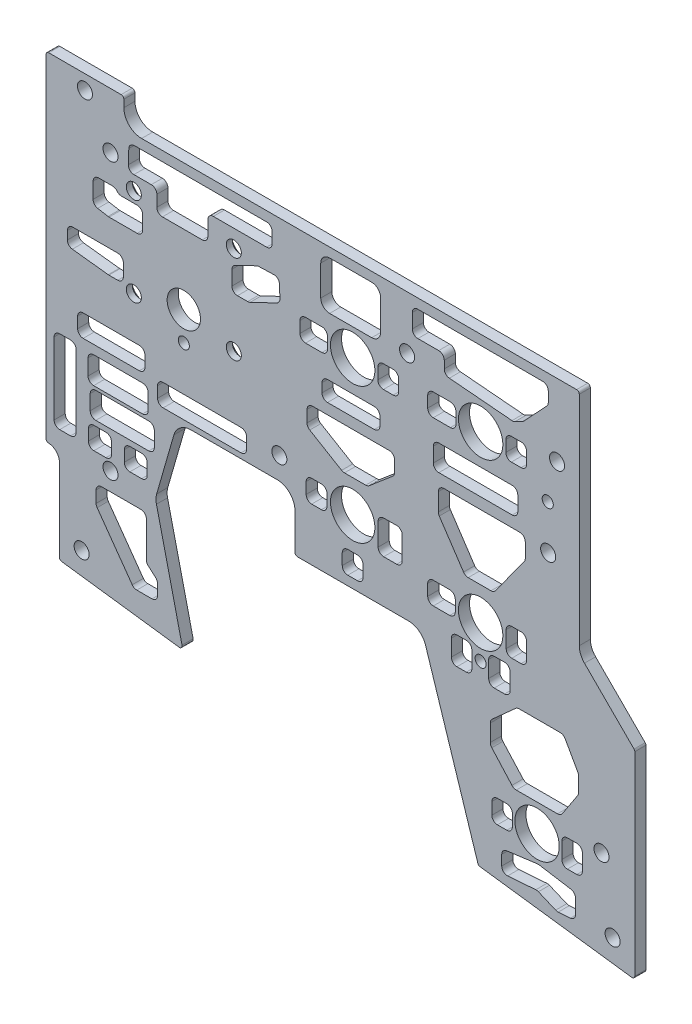
SolidWorks part; units mm, degrees
ref_plane "Front Plane" through (0, 0, 0) normal (0, 0, 1) x (1, 0, 0)
ref_plane "Top Plane" through (0, 0, 0) normal (0, 1, 0) x (1, 0, 0)
ref_plane "Right Plane" through (0, 0, 0) normal (1, 0, 0) x (0, 0, -1)
sketch "Sketch1" plane through (0, 0, 0) normal (0, 0, 1) x (1, 0, 0)
  line L16 (3.81, -91.8845) -> (3.81, -115.4033)
  line L17 (4.4725, -116.1588) -> (38.0231, -120.5758)
  line L18 (38.8645, -119.6465) -> (31.5446, -88.4134)
  line L19 (31.6093, -85.8475) -> (36.5334, -68.7608)
  line L20 (41.4148, -65.0875) -> (66.04, -65.0875)
  line L21 (71.12, -70.1675) -> (71.12, -80.518)
  line L22 (71.882, -81.28) -> (103.6122, -81.28)
  line L23 (108.4484, -84.805) -> (123.4233, -131.3792)
  line L24 (124.0493, -131.9014) -> (167.4135, -137.6104)
  line L25 (168.275, -136.8549) -> (168.275, -81.3036)
  line L26 (168.0518, -80.7647) -> (153.8879, -66.6008)
  line L27 (152.4, -63.0087) -> (152.4, -0.762)
  line L28 (151.638, 0) -> (27.305, 0)
  line L29 (22.225, 5.08) -> (22.225, 7.1755)
  line L30 (21.463, 7.9375) -> (0.762, 7.9375)
  line L31 (0, 7.1755) -> (0, -87.9495)
  line L32 (3.81, -91.8845) -> (3.81, -115.4033)
  line L33 (4.4725, -116.1588) -> (38.0231, -120.5758)
  line L34 (38.8645, -119.6465) -> (31.5446, -88.4134)
  line L35 (31.6093, -85.8475) -> (36.5334, -68.7608)
  line L36 (41.4148, -65.0875) -> (66.04, -65.0875)
  line L37 (71.12, -70.1675) -> (71.12, -80.518)
  line L38 (71.882, -81.28) -> (103.6122, -81.28)
  line L39 (108.4484, -84.805) -> (123.4233, -131.3792)
  line L40 (124.0493, -131.9014) -> (167.4135, -137.6104)
  line L41 (168.275, -136.8549) -> (168.275, -81.3036)
  line L42 (168.0518, -80.7647) -> (153.8879, -66.6008)
  line L43 (152.4, -63.0087) -> (152.4, -0.762)
  line L44 (151.638, 0) -> (27.305, 0)
  line L45 (22.225, 5.08) -> (22.225, 7.1755)
  line L46 (21.463, 7.9375) -> (0.762, 7.9375)
  line L47 (0, 7.1755) -> (0, -87.9495)
  arc A17 (3.81, -91.8845) -> (0.7374, -88.7112) centre (0.635, -91.8845) ccw
  arc A18 (3.81, -115.4033) -> (4.4725, -116.1588) centre (4.572, -115.4033) ccw
  arc A19 (38.0231, -120.5758) -> (38.8645, -119.6465) centre (38.1226, -119.8204) ccw
  arc A20 (31.6093, -85.8475) -> (31.5446, -88.4134) centre (36.4906, -87.2542) ccw
  arc A21 (41.4148, -65.0875) -> (36.5334, -68.7608) centre (41.4148, -70.1675) ccw
  arc A22 (71.12, -70.1675) -> (66.04, -65.0875) centre (66.04, -70.1675) ccw
  arc A23 (71.12, -80.518) -> (71.882, -81.28) centre (71.882, -80.518) ccw
  arc A24 (108.4484, -84.805) -> (103.6122, -81.28) centre (103.6122, -86.36) ccw
  arc A25 (123.4233, -131.3792) -> (124.0493, -131.9014) centre (124.1487, -131.1459) ccw
  arc A26 (167.4135, -137.6104) -> (168.275, -136.8549) centre (167.513, -136.8549) ccw
  arc A27 (168.275, -81.3036) -> (168.0518, -80.7647) centre (167.513, -81.3036) ccw
  arc A28 (152.4, -63.0087) -> (153.8879, -66.6008) centre (157.48, -63.0087) ccw
  arc A29 (152.4, -0.762) -> (151.638, 0) centre (151.638, -0.762) ccw
  arc A30 (22.225, 5.08) -> (27.305, 0) centre (27.305, 5.08) ccw
  arc A31 (22.225, 7.1755) -> (21.463, 7.9375) centre (21.463, 7.1755) ccw
  arc A32 (0.762, 7.9375) -> (0, 7.1755) centre (0.762, 7.1755) ccw
  arc A33 (0, -87.9495) -> (0.7374, -88.7112) centre (0.762, -87.9495) ccw
  arc A34 (3.81, -91.8845) -> (0.7374, -88.7112) centre (0.635, -91.8845) ccw
  arc A35 (3.81, -115.4033) -> (4.4725, -116.1588) centre (4.572, -115.4033) ccw
  arc A36 (38.0231, -120.5758) -> (38.8645, -119.6465) centre (38.1226, -119.8204) ccw
  arc A37 (31.6093, -85.8475) -> (31.5446, -88.4134) centre (36.4906, -87.2542) ccw
  arc A38 (41.4148, -65.0875) -> (36.5334, -68.7608) centre (41.4148, -70.1675) ccw
  arc A39 (71.12, -70.1675) -> (66.04, -65.0875) centre (66.04, -70.1675) ccw
  arc A40 (71.12, -80.518) -> (71.882, -81.28) centre (71.882, -80.518) ccw
  arc A41 (108.4484, -84.805) -> (103.6122, -81.28) centre (103.6122, -86.36) ccw
  arc A42 (123.4233, -131.3792) -> (124.0493, -131.9014) centre (124.1487, -131.1459) ccw
  arc A43 (167.4135, -137.6104) -> (168.275, -136.8549) centre (167.513, -136.8549) ccw
  arc A44 (168.275, -81.3036) -> (168.0518, -80.7647) centre (167.513, -81.3036) ccw
  arc A45 (152.4, -63.0087) -> (153.8879, -66.6008) centre (157.48, -63.0087) ccw
  arc A46 (152.4, -0.762) -> (151.638, 0) centre (151.638, -0.762) ccw
  arc A47 (22.225, 5.08) -> (27.305, 0) centre (27.305, 5.08) ccw
  arc A48 (22.225, 7.1755) -> (21.463, 7.9375) centre (21.463, 7.1755) ccw
  arc A49 (0.762, 7.9375) -> (0, 7.1755) centre (0.762, 7.1755) ccw
  arc A50 (0, -87.9495) -> (0.7374, -88.7112) centre (0.762, -87.9495) ccw
  dimension "D1" = 0
extrude "Boss-Extrude1" add sketch "Sketch1" against normal blind 3.175
hole_wizard "#6 Clearance Hole1" positions "Sketch3" profile "Sketch2" hole size "#6" standard "ANSI Inch" end condition through all
sketch "Sketch3" plane through (0, 0, -3.175) normal (0, 0, -1) x (-1, 0, 0)
  point P0 (-11.1125, 3.81)
  point P3 (-18.415, -7.9375)
  point P6 (-103.1875, -15.24)
  point P9 (-143.51, -44.45)
  point P12 (-158.75, -111.125)
  point P15 (-18.415, -86.741)
  point P18 (-66.675, -58.7375)
  point P21 (-10.16, -110.5028)
  point P25 (-146.05, -20.6375)
  point P28 (-161.925, -130.483)
sketch "Sketch2" plane through (11.1125, 3.81, -3.175) normal (1, 0, 0) x (0, 1, 0)
  line L0 (0, 0) -> (0, 3.175)
  line L1 (0, 3.175) -> (2.1526, 3.175)
  line L2 (2.1526, 3.175) -> (2.1526, 0)
  line L5 (2.1526, 0) -> (0, 0)
  line L11 (0, -6.35) -> (0, 107.95) construction
  dimension "Thru Hole Dia." = 4.3053
  dimension "Thru Hole Depth" = 3.175
sketch "Sketch4" plane through (0, 0, -3.175) normal (0, 0, -1) x (-1, 0, 0)
  circle A0 centre (-140.335, -115.57) radius 6.35
  circle A1 centre (-124.206, -71.4375) radius 6.35
  circle A2 centre (-87.63, -62.992) radius 6.35
  circle A3 centre (-87.63, -24.13) radius 6.35
  circle A4 centre (-124.206, -24.13) radius 6.35
  circle A5 centre (-124.206, -80.9625) radius 1.5875
  circle A6 centre (-39.37, -36.322) radius 4.7625
  dimension "D1" = 12.7
  dimension "D2" = 3.175
  dimension "D4" = 9.525
  dimension "D3" = 9.525
extrude "Cut-Extrude1" cut sketch "Sketch4" against normal through all
hole_wizard "CSK for #6 Flat Head Machine Screw (100)1" positions "Sketch6" profile "Sketch5" countersink size "#6" standard "ANSI Inch" end condition through all
sketch "Sketch6" plane through (0, 0, -3.175) normal (0, 0, -1) x (-1, 0, 0)
  point P0 (-53.6575, -14.097)
  point P2 (-25.0825, -14.097)
  point P4 (-25.0825, -39.497)
  point P6 (-53.6575, -39.497)
sketch "Sketch5" plane through (53.6575, -14.097, -3.175) normal (1, 0, 0) x (0, 1, 0)
  line L0 (0, 0) -> (0, 3.175)
  line L1 (0, 3.175) -> (2.1526, 3.175)
  line L2 (2.1526, 3.175) -> (2.1526, 1.4209)
  line L3 (2.1526, 1.4209) -> (3.846, 0)
  line L5 (3.846, 0) -> (0, 0)
  line L6 (-2.1526, 1.4209) -> (-3.846, 0) construction
  line L11 (0, -6.35) -> (0, 107.95) construction
  dimension "Thru Hole Dia." = 4.3053
  dimension "Thru Hole Depth" = 3.175
  dimension "Near C'Sink Dia." = 7.692
  dimension "Near C'Sink Angle" = 100
hole_wizard "#0 Clearance Hole1" positions "Sketch7" profile "Sketch8" hole size "#0" standard "ANSI Inch" end condition through all
sketch "Sketch7" plane through (0, 0, -9.525) normal (0, 0, -1) x (-1, 0, 0)
  point P0 (-39.37, -44.577)
sketch "Sketch8" plane through (39.37, -44.577, -9.525) normal (1, 0, 0) x (0, 1, 0)
  line L0 (0, 0) -> (0, 9.525)
  line L1 (0, 9.525) -> (0.9271, 9.525)
  line L2 (0.9271, 9.525) -> (0.9271, 0)
  line L3 (0.9271, 0) -> (0, 0)
  line L4 (0, -6.35) -> (0, 107.95) construction
  dimension "Thru Hole Dia." = 1.8542
  dimension "Thru Hole Depth" = 9.525
hole_wizard "1/8 (0.125) Diameter Hole1" positions "Sketch9" profile "Sketch10" hole size "1/8" standard "ANSI Inch" end condition through all
sketch "Sketch9" plane through (0, 0, 0) normal (0, 0, 1) x (1, 0, 0)
  point P0 (39.37, -44.577)
sketch "Sketch10" plane through (39.37, -44.577, 0) normal (1, 0, 0) x (0, -1, 0)
  line L0 (0, 0) -> (0, 3.175)
  line L1 (0, 3.175) -> (1.5875, 3.175)
  line L2 (1.5875, 3.175) -> (1.5875, 0)
  line L5 (1.5875, 0) -> (0, 0)
  line L11 (0, -6.35) -> (0, 107.95) construction
  dimension "Thru Hole Dia." = 3.175
  dimension "Thru Hole Depth" = 3.175
sketch "Sketch17" plane through (0, 0, 0) normal (0, 0, -1) x (-1, 0, 0)
  line L0 (-141.9544, -2.7948) -> (-106.2662, -2.7948)
  line L1 (-104.6787, -4.3823) -> (-104.6787, -8.4606)
  line L2 (-106.2662, -10.0481) -> (-112.2209, -10.0481)
  line L3 (-113.8084, -11.6356) -> (-113.8084, -13.7762)
  line L4 (-115.259, -15.3578) -> (-133.159, -16.9076)
  line L5 (-134.0131, -16.7423) -> (-136.0874, -15.6921)
  line L6 (-136.5298, -15.36) -> (-143.114, -8.3185)
  line L7 (-143.5419, -7.2342) -> (-143.5419, -4.3823)
  line L8 (-93.0669, -2.7076) -> (-81.0441, -2.7076)
  line L9 (-78.5041, -5.2476) -> (-78.5041, -13.8956)
  line L10 (-81.0441, -16.4356) -> (-93.0669, -16.4356)
  line L11 (-95.6069, -13.8956) -> (-95.6069, -5.2476)
  line L12 (-72.5612, -22.437) -> (-72.5612, -25.637)
  line L13 (-74.1487, -27.2245) -> (-78.851, -27.2245)
  line L14 (-80.4385, -25.637) -> (-80.4385, -22.437)
  line L15 (-74.1487, -20.8495) -> (-78.851, -20.8495)
  line L16 (-99.2018, -21.1963) -> (-96.4213, -21.1963)
  line L17 (-94.8338, -22.7838) -> (-94.8338, -25.9818)
  line L18 (-96.4213, -27.5693) -> (-99.2018, -27.5693)
  line L19 (-100.7893, -25.9818) -> (-100.7893, -22.7838)
  line L20 (-109.0792, -22.6549) -> (-109.0792, -25.8549)
  line L21 (-110.6667, -27.4424) -> (-115.5536, -27.4424)
  line L22 (-117.1411, -25.8549) -> (-117.1411, -22.6549)
  line L23 (-110.6667, -21.0674) -> (-115.5536, -21.0674)
  line L24 (-135.7738, -20.8814) -> (-132.9933, -20.8814)
  line L25 (-131.4058, -22.4689) -> (-131.4058, -25.667)
  line L26 (-132.9933, -27.2545) -> (-135.7738, -27.2545)
  line L27 (-137.3613, -25.667) -> (-137.3613, -22.4689)
  line L28 (-93.8189, -33.0853) -> (-80.4385, -33.0853)
  line L29 (-78.851, -34.6728) -> (-78.851, -37.1954)
  line L30 (-80.4385, -38.7829) -> (-93.8189, -38.7829)
  line L31 (-95.4064, -34.6728) -> (-95.4064, -37.1954)
  line L32 (-133.2346, -32.9063) -> (-112.2542, -32.9063)
  line L33 (-110.6667, -34.4938) -> (-110.6667, -38.6545)
  line L34 (-112.2542, -40.242) -> (-133.2346, -40.242)
  line L35 (-134.8221, -38.6545) -> (-134.8221, -34.4938)
  line L36 (-98.0498, -41.8469) -> (-76.1717, -41.8469)
  line L37 (-74.5842, -43.4344) -> (-74.5842, -46.7771)
  line L38 (-75.3596, -48.1412) -> (-84.4657, -53.5626)
  line L39 (-85.2778, -53.7861) -> (-91.3474, -53.7861)
  line L40 (-92.3756, -53.4081) -> (-99.0779, -47.711)
  line L41 (-99.6373, -46.5014) -> (-99.6373, -43.4344)
  line L42 (-135.3789, -43.4344) -> (-113.699, -43.4344)
  line L43 (-112.1115, -45.0219) -> (-112.1115, -50.0429)
  line L44 (-112.3789, -50.9245) -> (-119.3229, -61.3222)
  line L45 (-120.6431, -62.0281) -> (-127.1632, -62.0281)
  line L46 (-128.4485, -61.3724) -> (-136.6641, -50.0405)
  line L47 (-136.9664, -49.1087) -> (-136.9664, -45.0219)
  line L48 (-55.7285, -57.3176) -> (-33.4587, -57.3176)
  line L49 (-31.8712, -58.9051) -> (-31.8712, -62.02)
  line L50 (-33.4587, -63.6075) -> (-55.7285, -63.6075)
  line L51 (-57.316, -62.02) -> (-57.316, -58.9051)
  line L52 (-78.7021, -59.8174) -> (-75.9216, -59.8174)
  line L53 (-74.3341, -61.4049) -> (-74.3341, -64.603)
  line L54 (-75.9216, -66.1905) -> (-78.7021, -66.1905)
  line L55 (-80.2896, -64.603) -> (-80.2896, -61.4049)
  line L56 (-89.0189, -72.2548) -> (-86.2384, -72.2548)
  line L57 (-84.6509, -73.8423) -> (-84.6509, -77.0403)
  line L58 (-86.2384, -78.6278) -> (-89.0189, -78.6278)
  line L59 (-90.6064, -77.0403) -> (-90.6064, -73.8423)
  line L60 (-109.0756, -69.248) -> (-109.0756, -72.448)
  line L61 (-110.6631, -74.0355) -> (-115.3654, -74.0355)
  line L62 (-116.9529, -72.448) -> (-116.9529, -69.248)
  line L63 (-110.6631, -67.6605) -> (-115.3654, -67.6605)
  line L64 (-148.3701, -88.0766) -> (-151.9572, -94.4661)
  line L65 (-152.1698, -95.2794) -> (-152.1698, -99.4916)
  line L66 (-151.8961, -100.4052) -> (-147.5598, -106.9917)
  line L68 (-146.1721, -107.7395) -> (-134.3926, -107.7395)
  line L70 (-133.1575, -107.1893) -> (-127.3956, -100.785)
  line L71 (-126.9693, -99.6738) -> (-126.9693, -94.8668)
  line L72 (-127.5195, -93.6317) -> (-134.1629, -87.6548)
  line L73 (-135.2742, -87.2285) -> (-146.9213, -87.2285)
  line L74 (-137.3613, -69.4742) -> (-137.3613, -74.1715)
  line L75 (-135.7738, -75.759) -> (-133.0932, -75.759)
  line L76 (-131.5057, -74.1715) -> (-131.5057, -69.4818)
  line L77 (-133.0887, -67.8943) -> (-135.7692, -67.8867)
  line L78 (-132.6264, -79.3569) -> (-132.6264, -84.055)
  line L79 (-131.0389, -85.6425) -> (-128.0874, -85.6425)
  line L80 (-126.4999, -84.055) -> (-126.4999, -79.3653)
  line L81 (-128.0829, -77.7778) -> (-131.0344, -77.7694)
  line L82 (-121.6938, -79.414) -> (-121.6938, -84.1113)
  line L83 (-120.1063, -85.6988) -> (-117.4258, -85.6988)
  line L84 (-115.8383, -84.1113) -> (-115.8383, -79.4216)
  line L85 (-117.4212, -77.8341) -> (-120.1018, -77.8265)
  line L86 (-101.7978, -60.9375) -> (-101.7978, -67.3473)
  line L87 (-100.2103, -68.9348) -> (-96.4976, -68.9348)
  line L88 (-94.9101, -67.3473) -> (-94.9101, -60.9481)
  line L89 (-96.4931, -59.3606) -> (-100.2058, -59.35)
  line L90 (-153.2801, -113.8454) -> (-153.2801, -118.4115)
  line L91 (-151.6926, -119.999) -> (-149.0121, -119.999)
  line L92 (-147.4246, -118.4115) -> (-147.4246, -113.853)
  line L93 (-149.0076, -112.2655) -> (-151.6881, -112.2579)
  line L94 (-133.2696, -114.0603) -> (-133.2696, -117.4522)
  line L95 (-131.6821, -119.0397) -> (-129.0016, -119.0397)
  line L96 (-127.4141, -117.4522) -> (-127.4141, -114.0679)
  line L97 (-128.997, -112.4804) -> (-131.6776, -112.4728)
  line L98 (-150.0084, -124.4751) -> (-140.8902, -122.9925)
  line L99 (-140.4256, -122.9858) -> (-131.6139, -124.1607)
  line L100 (-130.2362, -125.7343) -> (-130.2362, -128.6297)
  line L101 (-131.9392, -130.213) -> (-139.9781, -129.6268)
  line L102 (-140.7126, -129.7482) -> (-145.6471, -131.838)
  line L103 (-146.3817, -131.9595) -> (-149.8691, -131.7052)
  line L104 (-151.3411, -130.1219) -> (-151.3411, -126.042)
  line L105 (-63.0404, -2.7948) -> (-25.2277, -2.7948)
  line L106 (-23.641, -4.3315) -> (-23.5105, -8.4099)
  line L107 (-25.0972, -10.0481) -> (-30.0725, -10.0481)
  line L108 (-31.66, -11.6356) -> (-31.66, -14.8481)
  line L109 (-33.2475, -16.4356) -> (-44.6401, -16.4356)
  line L110 (-46.2276, -14.8481) -> (-46.2276, -10.6224)
  line L111 (-47.8151, -9.0349) -> (-63.0404, -9.0349)
  line L112 (-64.6279, -7.4474) -> (-64.6279, -4.3823)
  line L113 (-14.7591, -23.5708) -> (-17.7234, -24.0903)
  line L114 (-17.9974, -24.1142) -> (-26.0381, -24.1142)
  line L115 (-27.6256, -22.5267) -> (-27.6256, -18.7366)
  line L116 (-26.0381, -17.1491) -> (-21.5632, -17.1491)
  line L117 (-20.4504, -16.6939) -> (-20.1204, -16.3695)
  line L118 (-19.0076, -15.9142) -> (-15.0331, -15.9142)
  line L119 (-13.4456, -17.5017) -> (-13.4456, -22.0071)
  line L120 (-7.6875, -31.7843) -> (-20.4927, -31.7843)
  line L121 (-22.0802, -33.3718) -> (-22.0802, -36.9105)
  line L122 (-20.4927, -38.498) -> (-17.9504, -38.498)
  line L123 (-17.7686, -38.4875) -> (-7.5058, -37.3048)
  line L124 (-6.1, -35.7277) -> (-6.1, -33.3718)
  line L125 (-54.0177, -18.0353) -> (-60.157, -15.0963)
  line L126 (-60.7931, -14.9415) -> (-65.0805, -14.8081)
  line L127 (-66.7166, -16.3454) -> (-66.8282, -19.9294)
  line L128 (-65.9269, -21.4107) -> (-58.3022, -25.0607)
  line L129 (-57.6167, -25.2163) -> (-54.7032, -25.2163)
  line L130 (-53.1157, -23.6288) -> (-53.1157, -19.4672)
  line L131 (-24.6224, -111.8142) -> (-14.5986, -97.7476)
  line L132 (-14.304, -96.8263) -> (-14.304, -93.5113)
  line L133 (-2.2976, -61.6269) -> (-2.2976, -82.1859)
  line L134 (-3.8851, -83.7734) -> (-6.9926, -83.7734)
  line L135 (-8.5801, -82.1859) -> (-8.5801, -61.6269)
  line L136 (-6.9926, -60.0394) -> (-3.8851, -60.0394)
  line L137 (-15.8915, -91.9238) -> (-27.0858, -91.9238)
  line L138 (-28.6733, -93.5113) -> (-28.6733, -103.656)
  line L139 (-29.2117, -104.8474) -> (-31.3328, -106.7152)
  line L140 (-31.8712, -107.9067) -> (-31.8712, -110.8929)
  line L141 (-30.2837, -112.4804) -> (-25.9153, -112.4804)
  line L142 (-26.655, -51.5392) -> (-10.6039, -51.5392)
  line L143 (-9.0164, -53.1267) -> (-9.0164, -56.2416)
  line L144 (-10.6039, -57.8291) -> (-26.655, -57.8291)
  line L145 (-28.2425, -56.2416) -> (-28.2425, -53.1267)
  line L146 (-27.6052, -60.385) -> (-13.5866, -60.385)
  line L147 (-11.9991, -61.9725) -> (-11.9991, -66.4544)
  line L148 (-13.5866, -68.0419) -> (-27.6052, -68.0419)
  line L149 (-29.1927, -66.4544) -> (-29.1927, -61.9725)
  line L150 (-29.347, -68.9032) -> (-14.2014, -68.9032)
  line L151 (-12.6139, -70.4907) -> (-12.6139, -74.7412)
  line L152 (-14.2014, -76.3287) -> (-29.347, -76.3287)
  line L153 (-30.9345, -74.7412) -> (-30.9345, -70.4907)
  line L154 (-27.3287, -77.9076) -> (-23.9481, -77.9076)
  line L155 (-22.3606, -79.4951) -> (-22.3606, -82.61)
  line L156 (-23.9481, -84.1975) -> (-27.3287, -84.1975)
  line L157 (-28.9162, -82.61) -> (-28.9162, -79.4951)
  line L158 (-17.1192, -77.821) -> (-13.667, -77.821)
  line L159 (-12.0795, -79.4085) -> (-12.0795, -82.5234)
  line L160 (-13.667, -84.1109) -> (-17.1192, -84.1109)
  line L161 (-18.7067, -82.5234) -> (-18.7067, -79.4085)
  arc A0 (-106.2662, -2.7948) -> (-104.6787, -4.3823) centre (-106.2662, -4.3823) cw
  arc A1 (-104.6787, -8.4606) -> (-106.2662, -10.0481) centre (-106.2662, -8.4606) cw
  arc A2 (-112.2209, -10.0481) -> (-113.8084, -11.6356) centre (-112.2209, -11.6356) ccw
  arc A3 (-113.8084, -13.7762) -> (-115.259, -15.3578) centre (-115.3959, -13.7762) cw
  arc A4 (-133.159, -16.9076) -> (-134.0131, -16.7423) centre (-133.296, -15.326) cw
  arc A5 (-136.0874, -15.6921) -> (-136.5298, -15.36) centre (-135.3703, -14.2758) cw
  arc A6 (-143.114, -8.3185) -> (-143.5419, -7.2342) centre (-141.9544, -7.2342) cw
  arc A7 (-141.9544, -2.7948) -> (-143.5419, -4.3823) centre (-141.9544, -4.3823) ccw
  arc A8 (-81.0441, -2.7076) -> (-78.5041, -5.2476) centre (-81.0441, -5.2476) cw
  arc A9 (-78.5041, -13.8956) -> (-81.0441, -16.4356) centre (-81.0441, -13.8956) cw
  arc A10 (-93.0669, -16.4356) -> (-95.6069, -13.8956) centre (-93.0669, -13.8956) cw
  arc A11 (-93.0669, -2.7076) -> (-95.6069, -5.2476) centre (-93.0669, -5.2476) ccw
  arc A12 (-72.5612, -22.437) -> (-74.1487, -20.8495) centre (-74.1487, -22.437) ccw
  arc A13 (-72.5612, -25.637) -> (-74.1487, -27.2245) centre (-74.1487, -25.637) cw
  arc A14 (-78.851, -27.2245) -> (-80.4385, -25.637) centre (-78.851, -25.637) cw
  arc A15 (-80.4385, -22.437) -> (-78.851, -20.8495) centre (-78.851, -22.437) cw
  arc A16 (-96.4213, -21.1963) -> (-94.8338, -22.7838) centre (-96.4213, -22.7838) cw
  arc A17 (-94.8338, -25.9818) -> (-96.4213, -27.5693) centre (-96.4213, -25.9818) cw
  arc A18 (-99.2018, -27.5693) -> (-100.7893, -25.9818) centre (-99.2018, -25.9818) cw
  arc A19 (-99.2018, -21.1963) -> (-100.7893, -22.7838) centre (-99.2018, -22.7838) ccw
  arc A20 (-109.0792, -22.6549) -> (-110.6667, -21.0674) centre (-110.6667, -22.6549) ccw
  arc A21 (-109.0792, -25.8549) -> (-110.6667, -27.4424) centre (-110.6667, -25.8549) cw
  arc A22 (-115.5536, -27.4424) -> (-117.1411, -25.8549) centre (-115.5536, -25.8549) cw
  arc A23 (-117.1411, -22.6549) -> (-115.5536, -21.0674) centre (-115.5536, -22.6549) cw
  arc A24 (-132.9933, -20.8814) -> (-131.4058, -22.4689) centre (-132.9933, -22.4689) cw
  arc A25 (-131.4058, -25.667) -> (-132.9933, -27.2545) centre (-132.9933, -25.667) cw
  arc A26 (-135.7738, -27.2545) -> (-137.3613, -25.667) centre (-135.7738, -25.667) cw
  arc A27 (-135.7738, -20.8814) -> (-137.3613, -22.4689) centre (-135.7738, -22.4689) ccw
  arc A28 (-80.4385, -33.0853) -> (-78.851, -34.6728) centre (-80.4385, -34.6728) cw
  arc A29 (-78.851, -37.1954) -> (-80.4385, -38.7829) centre (-80.4385, -37.1954) cw
  arc A30 (-93.8189, -38.7829) -> (-95.4064, -37.1954) centre (-93.8189, -37.1954) cw
  arc A31 (-93.8189, -33.0853) -> (-95.4064, -34.6728) centre (-93.8189, -34.6728) ccw
  arc A32 (-112.2542, -32.9063) -> (-110.6667, -34.4938) centre (-112.2542, -34.4938) cw
  arc A33 (-110.6667, -38.6545) -> (-112.2542, -40.242) centre (-112.2542, -38.6545) cw
  arc A34 (-133.2346, -40.242) -> (-134.8221, -38.6545) centre (-133.2346, -38.6545) cw
  arc A35 (-133.2346, -32.9063) -> (-134.8221, -34.4938) centre (-133.2346, -34.4938) ccw
  arc A36 (-91.3474, -53.7861) -> (-92.3756, -53.4081) centre (-91.3474, -52.1986) cw
  arc A37 (-84.4657, -53.5626) -> (-85.2778, -53.7861) centre (-85.2778, -52.1986) cw
  arc A38 (-74.5842, -46.7771) -> (-75.3596, -48.1412) centre (-76.1717, -46.7771) cw
  arc A39 (-76.1717, -41.8469) -> (-74.5842, -43.4344) centre (-76.1717, -43.4344) cw
  arc A40 (-98.0498, -41.8469) -> (-99.6373, -43.4344) centre (-98.0498, -43.4344) ccw
  arc A41 (-99.0779, -47.711) -> (-99.6373, -46.5014) centre (-98.0498, -46.5014) cw
  arc A42 (-113.699, -43.4344) -> (-112.1115, -45.0219) centre (-113.699, -45.0219) cw
  arc A43 (-112.1115, -50.0429) -> (-112.3789, -50.9245) centre (-113.699, -50.0429) cw
  arc A44 (-119.3229, -61.3222) -> (-120.6431, -62.0281) centre (-120.6431, -60.4406) cw
  arc A45 (-127.1632, -62.0281) -> (-128.4485, -61.3724) centre (-127.1632, -60.4406) cw
  arc A46 (-136.6641, -50.0405) -> (-136.9664, -49.1087) centre (-135.3789, -49.1087) cw
  arc A47 (-135.3789, -43.4344) -> (-136.9664, -45.0219) centre (-135.3789, -45.0219) ccw
  arc A48 (-33.4587, -57.3176) -> (-31.8712, -58.9051) centre (-33.4587, -58.9051) cw
  arc A49 (-31.8712, -62.02) -> (-33.4587, -63.6075) centre (-33.4587, -62.02) cw
  arc A50 (-55.7285, -63.6075) -> (-57.316, -62.02) centre (-55.7285, -62.02) cw
  arc A51 (-55.7285, -57.3176) -> (-57.316, -58.9051) centre (-55.7285, -58.9051) ccw
  arc A52 (-75.9216, -59.8174) -> (-74.3341, -61.4049) centre (-75.9216, -61.4049) cw
  arc A53 (-74.3341, -64.603) -> (-75.9216, -66.1905) centre (-75.9216, -64.603) cw
  arc A54 (-78.7021, -66.1905) -> (-80.2896, -64.603) centre (-78.7021, -64.603) cw
  arc A55 (-78.7021, -59.8174) -> (-80.2896, -61.4049) centre (-78.7021, -61.4049) ccw
  arc A56 (-86.2384, -72.2548) -> (-84.6509, -73.8423) centre (-86.2384, -73.8423) cw
  arc A57 (-84.6509, -77.0403) -> (-86.2384, -78.6278) centre (-86.2384, -77.0403) cw
  arc A58 (-89.0189, -78.6278) -> (-90.6064, -77.0403) centre (-89.0189, -77.0403) cw
  arc A59 (-89.0189, -72.2548) -> (-90.6064, -73.8423) centre (-89.0189, -73.8423) ccw
  arc A60 (-109.0756, -69.248) -> (-110.6631, -67.6605) centre (-110.6631, -69.248) ccw
  arc A61 (-109.0756, -72.448) -> (-110.6631, -74.0355) centre (-110.6631, -72.448) cw
  arc A62 (-115.3654, -74.0355) -> (-116.9529, -72.448) centre (-115.3654, -72.448) cw
  arc A63 (-116.9529, -69.248) -> (-115.3654, -67.6605) centre (-115.3654, -69.248) cw
  arc A64 (-134.1629, -87.6548) -> (-135.2742, -87.2285) centre (-135.2742, -88.8899) ccw
  arc A65 (-126.9693, -94.8668) -> (-127.5195, -93.6317) centre (-128.6308, -94.8668) ccw
  arc A66 (-127.3956, -100.785) -> (-126.9693, -99.6738) centre (-128.6308, -99.6738) ccw
  arc A67 (-134.3926, -107.7395) -> (-133.1575, -107.1893) centre (-134.3926, -106.0781) ccw
  arc A68 (-147.5598, -106.9917) -> (-146.1721, -107.7395) centre (-146.1721, -106.0781) ccw
  arc A69 (-152.1698, -99.4916) -> (-151.8961, -100.4052) centre (-150.5084, -99.4916) ccw
  arc A70 (-151.9572, -94.4661) -> (-152.1698, -95.2794) centre (-150.5084, -95.2794) ccw
  arc A71 (-148.3701, -88.0766) -> (-146.9213, -87.2285) centre (-146.9213, -88.8899) cw
  arc A72 (-137.3613, -69.4742) -> (-135.7692, -67.8867) centre (-135.7738, -69.4742) cw
  arc A73 (-131.5057, -69.4818) -> (-133.0887, -67.8943) centre (-133.0932, -69.4818) ccw
  arc A74 (-133.0932, -75.759) -> (-131.5057, -74.1715) centre (-133.0932, -74.1715) ccw
  arc A75 (-137.3613, -74.1715) -> (-135.7738, -75.759) centre (-135.7738, -74.1715) ccw
  arc A76 (-132.6264, -79.3569) -> (-131.0344, -77.7694) centre (-131.0389, -79.3569) cw
  arc A77 (-126.4999, -79.3653) -> (-128.0829, -77.7778) centre (-128.0874, -79.3653) ccw
  arc A78 (-128.0874, -85.6425) -> (-126.4999, -84.055) centre (-128.0874, -84.055) ccw
  arc A79 (-132.6264, -84.055) -> (-131.0389, -85.6425) centre (-131.0389, -84.055) ccw
  arc A80 (-121.6938, -79.414) -> (-120.1018, -77.8265) centre (-120.1063, -79.414) cw
  arc A81 (-115.8383, -79.4216) -> (-117.4212, -77.8341) centre (-117.4258, -79.4216) ccw
  arc A82 (-117.4258, -85.6988) -> (-115.8383, -84.1113) centre (-117.4258, -84.1113) ccw
  arc A83 (-121.6938, -84.1113) -> (-120.1063, -85.6988) centre (-120.1063, -84.1113) ccw
  arc A84 (-101.7978, -60.9375) -> (-100.2058, -59.35) centre (-100.2103, -60.9375) cw
  arc A85 (-94.9101, -60.9481) -> (-96.4931, -59.3606) centre (-96.4976, -60.9481) ccw
  arc A86 (-96.4976, -68.9348) -> (-94.9101, -67.3473) centre (-96.4976, -67.3473) ccw
  arc A87 (-101.7978, -67.3473) -> (-100.2103, -68.9348) centre (-100.2103, -67.3473) ccw
  arc A88 (-153.2801, -113.8454) -> (-151.6881, -112.2579) centre (-151.6926, -113.8454) cw
  arc A89 (-147.4246, -113.853) -> (-149.0076, -112.2655) centre (-149.0121, -113.853) ccw
  arc A90 (-149.0121, -119.999) -> (-147.4246, -118.4115) centre (-149.0121, -118.4115) ccw
  arc A91 (-153.2801, -118.4115) -> (-151.6926, -119.999) centre (-151.6926, -118.4115) ccw
  arc A92 (-133.2696, -114.0603) -> (-131.6776, -112.4728) centre (-131.6821, -114.0603) cw
  arc A93 (-127.4141, -114.0679) -> (-128.997, -112.4804) centre (-129.0016, -114.0679) ccw
  arc A94 (-129.0016, -119.0397) -> (-127.4141, -117.4522) centre (-129.0016, -117.4522) ccw
  arc A95 (-133.2696, -117.4522) -> (-131.6821, -119.0397) centre (-131.6821, -117.4522) ccw
  arc A96 (-140.8902, -122.9925) -> (-140.4256, -122.9858) centre (-140.6354, -124.5594) cw
  arc A97 (-131.6139, -124.1607) -> (-130.2362, -125.7343) centre (-131.8237, -125.7343) cw
  arc A98 (-130.2362, -128.6297) -> (-131.9392, -130.213) centre (-131.8237, -128.6297) cw
  arc A99 (-139.9781, -129.6268) -> (-140.7126, -129.7482) centre (-140.0935, -131.2101) ccw
  arc A100 (-145.6471, -131.838) -> (-146.3817, -131.9595) centre (-146.2662, -130.3762) cw
  arc A101 (-149.8691, -131.7052) -> (-151.3411, -130.1219) centre (-149.7536, -130.1219) cw
  arc A102 (-150.0084, -124.4751) -> (-151.3411, -126.042) centre (-149.7536, -126.042) ccw
  arc A103 (-63.0404, -2.7948) -> (-64.6279, -4.3823) centre (-63.0404, -4.3823) ccw
  arc A104 (-25.2277, -2.7948) -> (-23.641, -4.3315) centre (-25.2277, -4.3823) cw
  arc A105 (-23.5105, -8.4099) -> (-25.0972, -10.0481) centre (-25.0972, -8.4606) cw
  arc A106 (-30.0725, -10.0481) -> (-31.66, -11.6356) centre (-30.0725, -11.6356) ccw
  arc A107 (-31.66, -14.8481) -> (-33.2475, -16.4356) centre (-33.2475, -14.8481) cw
  arc A108 (-44.6401, -16.4356) -> (-46.2276, -14.8481) centre (-44.6401, -14.8481) cw
  arc A109 (-46.2276, -10.6224) -> (-47.8151, -9.0349) centre (-47.8151, -10.6224) ccw
  arc A110 (-63.0404, -9.0349) -> (-64.6279, -7.4474) centre (-63.0404, -7.4474) cw
  arc A111 (-23.9481, -77.9076) -> (-22.3606, -79.4951) centre (-23.9481, -79.4951) cw
  arc A112 (-21.5632, -17.1491) -> (-20.4504, -16.6939) centre (-21.5632, -15.5616) ccw
  arc A113 (-20.1204, -16.3695) -> (-19.0076, -15.9142) centre (-19.0076, -17.5017) cw
  arc A114 (-15.0331, -15.9142) -> (-13.4456, -17.5017) centre (-15.0331, -17.5017) cw
  arc A115 (-14.7591, -23.5708) -> (-13.4456, -22.0071) centre (-15.0331, -22.0071) ccw
  arc A116 (-17.7234, -24.0903) -> (-17.9974, -24.1142) centre (-17.9974, -22.5267) cw
  arc A117 (-26.0381, -24.1142) -> (-27.6256, -22.5267) centre (-26.0381, -22.5267) cw
  arc A118 (-27.6256, -18.7366) -> (-26.0381, -17.1491) centre (-26.0381, -18.7366) cw
  arc A119 (-20.4927, -31.7843) -> (-22.0802, -33.3718) centre (-20.4927, -33.3718) ccw
  arc A120 (-22.0802, -36.9105) -> (-20.4927, -38.498) centre (-20.4927, -36.9105) ccw
  arc A121 (-17.9504, -38.498) -> (-17.7686, -38.4875) centre (-17.9504, -36.9105) ccw
  arc A122 (-7.5058, -37.3048) -> (-6.1, -35.7277) centre (-7.6875, -35.7277) ccw
  arc A123 (-7.6875, -31.7843) -> (-6.1, -33.3718) centre (-7.6875, -33.3718) cw
  arc A124 (-58.3022, -25.0607) -> (-57.6167, -25.2163) centre (-57.6167, -23.6288) ccw
  arc A125 (-54.7032, -25.2163) -> (-53.1157, -23.6288) centre (-54.7032, -23.6288) ccw
  arc A126 (-54.0177, -18.0353) -> (-53.1157, -19.4672) centre (-54.7032, -19.4672) cw
  arc A127 (-60.157, -15.0963) -> (-60.7931, -14.9415) centre (-60.8425, -16.5282) ccw
  arc A128 (-65.0805, -14.8081) -> (-66.7166, -16.3454) centre (-65.1299, -16.3948) ccw
  arc A129 (-66.8282, -19.9294) -> (-65.9269, -21.4107) centre (-65.2414, -19.9788) ccw
  arc A130 (-6.9926, -83.7734) -> (-8.5801, -82.1859) centre (-6.9926, -82.1859) cw
  arc A131 (-2.2976, -82.1859) -> (-3.8851, -83.7734) centre (-3.8851, -82.1859) cw
  arc A132 (-3.8851, -60.0394) -> (-2.2976, -61.6269) centre (-3.8851, -61.6269) cw
  arc A133 (-8.5801, -61.6269) -> (-6.9926, -60.0394) centre (-6.9926, -61.6269) cw
  arc A134 (-14.304, -93.5113) -> (-15.8915, -91.9238) centre (-15.8915, -93.5113) ccw
  arc A135 (-14.5986, -97.7476) -> (-14.304, -96.8263) centre (-15.8915, -96.8263) ccw
  arc A136 (-24.6224, -111.8142) -> (-25.9153, -112.4804) centre (-25.9153, -110.8929) cw
  arc A137 (-31.8712, -110.8929) -> (-30.2837, -112.4804) centre (-30.2837, -110.8929) ccw
  arc A138 (-31.3328, -106.7152) -> (-31.8712, -107.9067) centre (-30.2837, -107.9067) ccw
  arc A139 (-28.6733, -103.656) -> (-29.2117, -104.8474) centre (-30.2608, -103.656) cw
  arc A140 (-27.0858, -91.9238) -> (-28.6733, -93.5113) centre (-27.0858, -93.5113) ccw
  arc A141 (-10.6039, -51.5392) -> (-9.0164, -53.1267) centre (-10.6039, -53.1267) cw
  arc A142 (-9.0164, -56.2416) -> (-10.6039, -57.8291) centre (-10.6039, -56.2416) cw
  arc A143 (-26.655, -57.8291) -> (-28.2425, -56.2416) centre (-26.655, -56.2416) cw
  arc A144 (-26.655, -51.5392) -> (-28.2425, -53.1267) centre (-26.655, -53.1267) ccw
  arc A145 (-13.5866, -60.385) -> (-11.9991, -61.9725) centre (-13.5866, -61.9725) cw
  arc A146 (-11.9991, -66.4544) -> (-13.5866, -68.0419) centre (-13.5866, -66.4544) cw
  arc A147 (-27.6052, -68.0419) -> (-29.1927, -66.4544) centre (-27.6052, -66.4544) cw
  arc A148 (-27.6052, -60.385) -> (-29.1927, -61.9725) centre (-27.6052, -61.9725) ccw
  arc A149 (-14.2014, -68.9032) -> (-12.6139, -70.4907) centre (-14.2014, -70.4907) cw
  arc A150 (-12.6139, -74.7412) -> (-14.2014, -76.3287) centre (-14.2014, -74.7412) cw
  arc A151 (-29.347, -76.3287) -> (-30.9345, -74.7412) centre (-29.347, -74.7412) cw
  arc A152 (-29.347, -68.9032) -> (-30.9345, -70.4907) centre (-29.347, -70.4907) ccw
  arc A153 (-22.3606, -82.61) -> (-23.9481, -84.1975) centre (-23.9481, -82.61) cw
  arc A154 (-27.3287, -84.1975) -> (-28.9162, -82.61) centre (-27.3287, -82.61) cw
  arc A155 (-27.3287, -77.9076) -> (-28.9162, -79.4951) centre (-27.3287, -79.4951) ccw
  arc A156 (-13.667, -77.821) -> (-12.0795, -79.4085) centre (-13.667, -79.4085) cw
  arc A157 (-12.0795, -82.5234) -> (-13.667, -84.1109) centre (-13.667, -82.5234) cw
  arc A158 (-17.1192, -84.1109) -> (-18.7067, -82.5234) centre (-17.1192, -82.5234) cw
  arc A159 (-17.1192, -77.821) -> (-18.7067, -79.4085) centre (-17.1192, -79.4085) ccw
  circle A160 centre (-143.3865, -31.863) radius 1.5875
  point P212 (-133.6525, -107.7395)
  point P215 (-147.0675, -107.7395)
  point P488 (-143.3865, -31.863)
  dimension "D1" = 1.5875
  dimension "D2" = 2.54
  dimension "D3" = 1.5875
  dimension "D4" = 1.5875
  dimension "D5" = 1.5875
  dimension "D6" = 1.5875
  dimension "D7" = 1.5875
  dimension "D8" = 1.5875
  dimension "D9" = 1.5875
  dimension "D10" = 1.5875
  dimension "D11" = 1.6614
  dimension "D12" = 1.5875
  dimension "D13" = 1.5875
  dimension "D14" = 1.5875
  dimension "D15" = 1.5875
  dimension "D16" = 1.5875
  dimension "D17" = 1.5875
  dimension "D18" = 1.5875
  dimension "D19" = 1.5875
  dimension "D20" = 3.175
extrude "Cut-Extrude3" cut sketch "Sketch17" along normal through all
